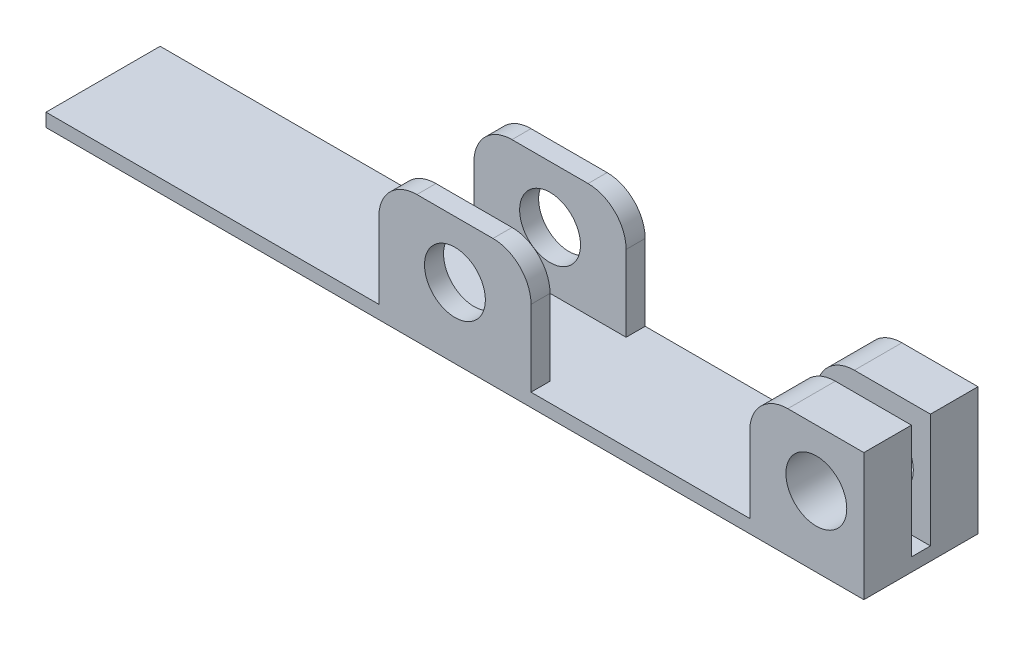
SolidWorks part; units mm, degrees
ref_plane "Front Plane" through (0, 0, 0) normal (0, 0, 1) x (1, 0, 0)
ref_plane "Top Plane" through (0, 0, 0) normal (0, 1, 0) x (1, 0, 0)
ref_plane "Right Plane" through (0, 0, 0) normal (1, 0, 0) x (0, 0, -1)
sketch "Sketch2" plane through (0, 0, 0) normal (0, 1, 0) x (1, 0, 0)
  line L1 (107.5, 15) -> (-107.5, 15)
  line L2 (107.5, 15) -> (107.5, -15)
  line L3 (107.5, -15) -> (-107.5, -15)
  line L4 (-107.5, 15) -> (-107.5, -15)
  line L5 (107.5, 15) -> (-107.5, -15) construction
  line L6 (107.5, -15) -> (-107.5, 15) construction
  point P0 (0, 0)
  dimension "D1" = 215
  dimension "D2" = 30
extrude "Boss-Extrude1" add sketch "Sketch2" along normal blind 3.5
sketch "HOLES TBD" plane through (0, 3.5, 0) normal (0, 1, 0) x (1, 0, 0)
  line L0 (100, 0) -> (-100, 0) construction
  circle A0 centre (-100, 0) radius 2.8385
  circle A1 centre (100, 0) radius 2.8385
  point P4 (0, 0)
  dimension "D2" = 5.6769
  dimension "D1" = 200
sketch "Sketch4" plane through (0, 3.5, 0) normal (0, 1, 0) x (1, 0, 0)
  line L0 (-107.5, -15) -> (107.5, -15) construction
  line L1 (107.5, -15) -> (77.5, -15)
  line L2 (107.5, -15) -> (107.5, -2.5)
  line L3 (107.5, -2.5) -> (77.5, -2.5)
  line L4 (77.5, -15) -> (77.5, -2.5)
  line L5 (107.5, -15) -> (77.5, -2.5) construction
  line L6 (107.5, -2.5) -> (77.5, -15) construction
  line L7 (-20, -15) -> (20, -15)
  line L8 (-20, -15) -> (-20, -10)
  line L9 (-20, -10) -> (20, -10)
  line L10 (20, -15) -> (20, -10)
  line L11 (-20, -15) -> (20, -10) construction
  line L12 (-20, -10) -> (20, -15) construction
  line L13 (0, 0) -> (0, -15) construction
  line L14 (-100, 0) -> (100, 0) construction
  line L15 (-20, 10) -> (20, 15) construction
  line L16 (-20, 15) -> (20, 10) construction
  line L17 (107.5, 2.5) -> (77.5, 15) construction
  line L18 (107.5, 15) -> (77.5, 2.5) construction
  line L19 (20, 15) -> (20, 10)
  line L20 (-20, 10) -> (20, 10)
  line L21 (-20, 15) -> (-20, 10)
  line L22 (-20, 15) -> (20, 15)
  line L23 (77.5, 15) -> (77.5, 2.5)
  line L24 (107.5, 2.5) -> (77.5, 2.5)
  line L25 (107.5, 15) -> (107.5, 2.5)
  line L26 (107.5, 15) -> (77.5, 15)
  point P4 (92.5, -8.75)
  point P10 (0, -12.5)
  point P28 (0, 12.5)
  point P29 (92.5, 8.75)
  dimension "D1" = 12.5
  dimension "D2" = 30
  dimension "D3" = 40
  dimension "D4" = 5
extrude "Boss-Extrude2" add sketch "Sketch4" along normal blind 30
sketch "Sketch5" plane through (0, 0, 15) normal (0, 0, 1) x (1, 0, 0)
  line L0 (0, 3.5) -> (0, 18.5) construction
  line L3 (0, 18.5) -> (95, 18.5) construction
  line L6 (20, 33.5) -> (20, 3.5) construction
  circle A0 centre (0, 18.5) radius 8
  circle A1 centre (95, 18.5) radius 8
  point P10 (20, 18.5)
  dimension "D1" = 16
  dimension "D2" = 16
  dimension "D3" = 95
extrude "Bearing holes" cut sketch "Sketch5" against normal through all
chamfer "Chamfer1" [suppressed] distance 5 angle 45
fillet "Fillet1" radius 10 6 edges at (-20, 33.5, 12.5) (-20, 33.5, -12.5) (20, 33.5, -12.5) (20, 33.5, 12.5) (77.5, 33.5, 8.75) (77.5, 33.5, -8.75)
